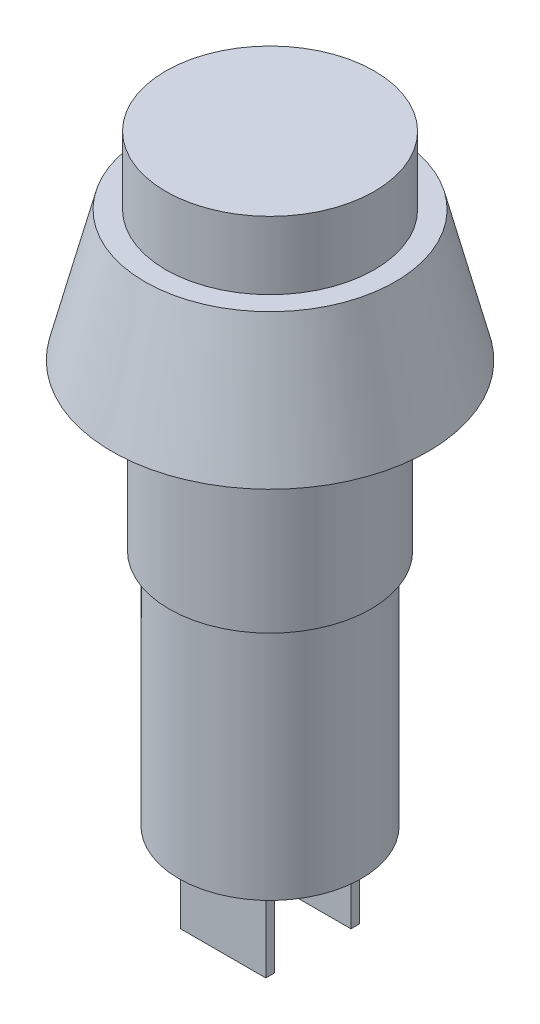
SolidWorks part; units mm, degrees
ref_plane "Спереди" through (0, 0, 0) normal (0, 0, 1) x (1, 0, 0)
ref_plane "Сверху" through (0, 0, 0) normal (0, 1, 0) x (1, 0, 0)
ref_plane "Справа" through (0, 0, 0) normal (1, 0, 0) x (0, 0, -1)
sketch "Эскиз1" plane through (0, 0, 0) normal (0, 1, 0) x (1, 0, 0)
  circle A0 centre (0, 0) radius 9.1
  circle A1 centre (0, 0) radius 7.2
sketch "Эскиз5" plane through (0, 0, 0) normal (0, 0, 1) x (1, 0, 0)
  line L0 (0, 0) -> (-9.1, 0) construction
  line L1 (7.2, 0) -> (-7.2, 0) construction
  line L2 (9.1, 0) -> (-9.1, 0) construction
  line L3 (-9.1, 0) -> (-7.2, 0) construction
  line L4 (-9.1, 0) -> (-9.1, 7.5) construction
  line L5 (-7.2, 0) -> (-7.2, 7.5) construction
  line L6 (-7.2, 7.5) -> (-9.1, 0)
  line L7 (0, 0) -> (0, 7.5) construction
  line L8 (0, 0) -> (0, 7.5)
  line L9 (0, 7.5) -> (-7.2, 7.5)
  line L10 (-9.1, 0) -> (0, 0)
revolve "Повернуть1" add sketch "Эскиз5" angle 360 about L8
sketch "Эскиз6" plane through (0, 7.5, 0) normal (0, 1, 0) x (1, 0, 0)
  circle A0 centre (0, 0) radius 6
extrude "Бобышка-Вытянуть3" add sketch "Эскиз6" along normal blind 3.9 contours A0
sketch "Эскиз7" plane through (0, 0, 0) normal (0, -1, 0) x (1, 0, 0)
  circle A0 centre (0, 0) radius 5.8
  point P3 (13.2056, -15.4145)
extrude "Бобышка-Вытянуть4" add sketch "Эскиз7" along normal blind 9.5
sketch "Эскиз8" plane through (0, -9.5, 0) normal (0, -1, 0) x (1, 0, 0)
  circle A0 centre (0, 0) radius 5.25
extrude "Бобышка-Вытянуть5" add sketch "Эскиз8" along normal blind 13.7
sketch "Эскиз9" plane through (0, -23.2, 0) normal (0, -1, 0) x (-1, 0, 0)
  line L0 (0, 0) -> (0, 2.2) construction
  line L1 (0, 0) -> (0, -2.2) construction
  line L2 (0, 2.2) -> (2.4489, 2.2) construction
  line L3 (0, -2.2) -> (2.4489, -2.2) construction
  line L4 (2.4489, 2.2) -> (-2.4497, 2.2)
  line L5 (2.4489, 2.2) -> (2.4489, 2.7004)
  line L6 (2.4489, 2.7004) -> (-2.4497, 2.7004)
  line L7 (-2.4497, 2.2) -> (-2.4497, 2.7004)
  line L9 (2.4489, -2.2) -> (-2.4497, -2.2)
  line L10 (2.4489, -2.2) -> (2.4489, -2.6956)
  line L11 (2.4489, -2.6956) -> (-2.4497, -2.6956)
  line L12 (-2.4497, -2.2) -> (-2.4497, -2.6956)
extrude "Бобышка-Вытянуть6" add sketch "Эскиз9" along normal blind 5
